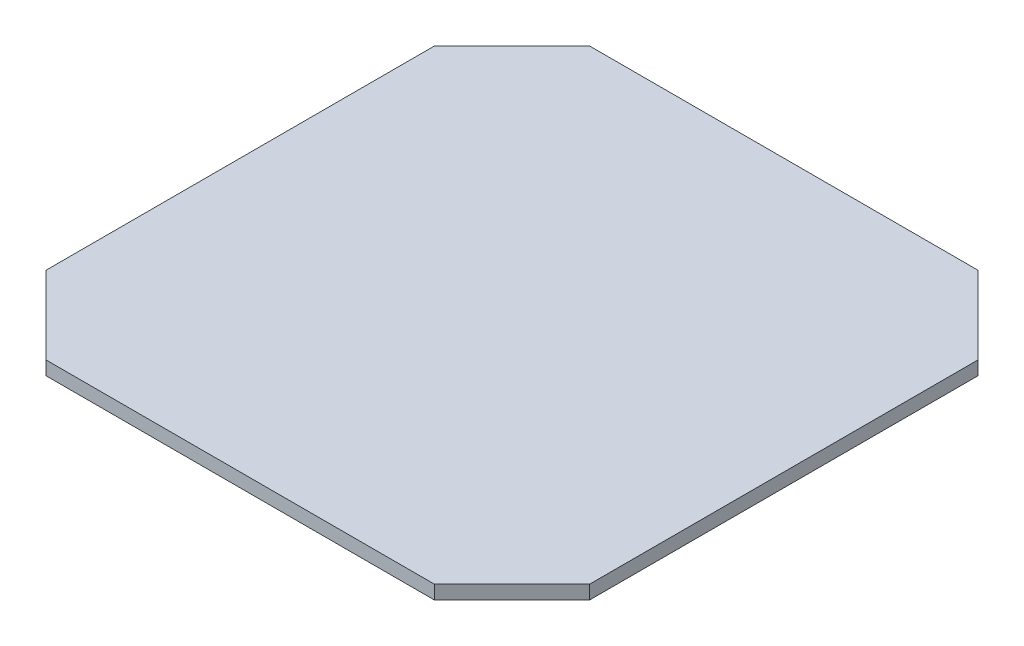
SolidWorks part; units mm, degrees
material "1060 Alloy"
ref_plane "Front Plane" through (0, 0, 0) normal (0, 0, 1) x (1, 0, 0)
ref_plane "Top Plane" through (0, 0, 0) normal (0, 1, 0) x (1, 0, 0)
ref_plane "Right Plane" through (0, 0, 0) normal (1, 0, 0) x (0, 0, -1)
sketch "Sketch1" plane through (0, 0, 0) normal (0, 1, 0) x (1, 0, 0)
  line L0 (-62.8618, -44.9013) -> (-44.9013, -62.8618)
  line L1 (-44.9013, -62.8618) -> (44.9013, -62.8618)
  line L2 (-62.8618, -44.9013) -> (-62.8618, 44.9013)
  line L3 (-44.9013, 62.8618) -> (44.9013, 62.8618)
  line L4 (62.8618, -44.9013) -> (62.8618, 44.9013)
  line L5 (-53.8815, -53.8815) -> (53.8815, 53.8815) construction
  line L6 (-53.8815, 53.8815) -> (53.8815, -53.8815) construction
  line L10 (-40.4112, -58.3717) -> (-58.3717, -40.4112) construction
  line L11 (-44.9013, 62.8618) -> (-62.8618, 44.9013)
  line L12 (62.8618, 44.9013) -> (44.9013, 62.8618)
  line L13 (44.9013, -62.8618) -> (62.8618, -44.9013)
  point P0 (0, 0)
  point P19 (0, 0)
  dimension "D3" = 135
  dimension "D4" = 4
  dimension "D1" = 152.4
extrude "Boss-Extrude1" add sketch "Sketch1" along normal blind 3.175
ref_axis "Axis1" through (0, 0, 0) along (0, 1, 0)
